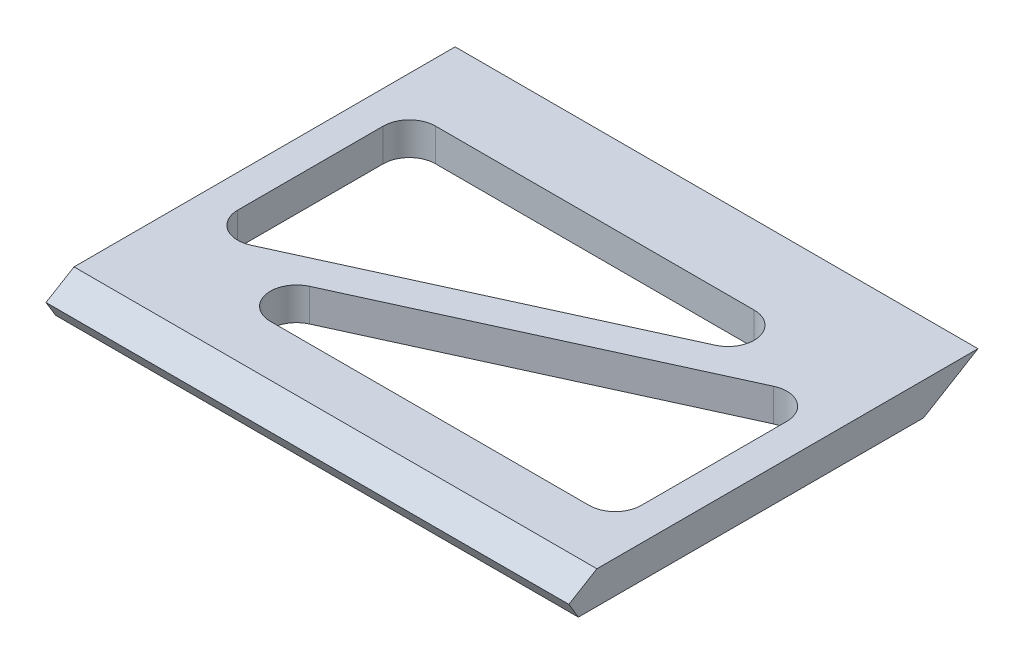
SolidWorks part; units mm, degrees
material "Balsa"
ref_plane "Front Plane" through (0, 0, 0) normal (0, 0, 1) x (1, 0, 0)
ref_plane "Top Plane" through (0, 0, 0) normal (0, 1, 0) x (1, 0, 0)
ref_plane "Right Plane" through (0, 0, 0) normal (1, 0, 0) x (0, 0, -1)
sketch "Sketch3" plane through (71.1933, 0, 0) normal (1, 0, 0) x (0, 0, -1)
  line L0 (56.968, 6.35) -> (46.3846, 0)
  line L1 (46.3846, 0) -> (-20.6804, 0)
  line L2 (-20.6804, 0) -> (-22.5302, 3.083)
  line L3 (-22.5302, 3.083) -> (-227.7008, 345.034) construction
  line L4 (56.968, 6.35) -> (63.7199, 10.4011) construction
  line L6 (-22.5302, 3.083) -> (-17.0851, 6.35)
  line L7 (-17.0851, 6.35) -> (56.968, 6.35)
extrude "Boss-Extrude2" add sketch "Sketch3" against normal up to surface (101.6 mm away)
sketch "Sketch4" plane through (0, 6.35, 0) normal (0, 1, 0) x (1, 0, 0)
  line L0 (-30.4067, -17.0851) -> (-30.4067, 56.968) construction
  line L1 (-18.9767, 41.728) -> (42.949, 41.728)
  line L2 (-24.0567, 36.648) -> (-24.0567, 8.3732)
  line L3 (-2.1624, -7.1791) -> (59.7633, -7.1791)
  line L4 (64.8433, 26.1757) -> (64.8433, -2.0991)
  line L5 (-30.4067, 56.968) -> (71.1933, 56.968) construction
  line L6 (71.1933, 56.968) -> (71.1933, -17.0851) construction
  line L7 (-30.4067, -17.0851) -> (71.1933, -17.0851) construction
  line L8 (-16.8668, 3.7521) -> (45.0589, 32.0269)
  line L9 (-4.2724, 2.522) -> (57.6533, 30.7968)
  line L10 (-29.6117, -5.5575) -> (68.6464, 39.3064)
  arc A0 (-4.2724, 2.522) -> (-2.1624, -7.1791) centre (-2.1624, -2.0991) ccw
  arc A1 (59.7633, -7.1791) -> (64.8433, -2.0991) centre (59.7633, -2.0991) ccw
  arc A2 (57.6533, 30.7968) -> (64.8433, 26.1757) centre (59.7633, 26.1757) cw
  arc A3 (45.0589, 32.0269) -> (42.949, 41.728) centre (42.949, 36.648) ccw
  arc A4 (-18.9767, 41.728) -> (-24.0567, 36.648) centre (-18.9767, 36.648) ccw
  arc A5 (-16.8668, 3.7521) -> (-24.0567, 8.3732) centre (-18.9767, 8.3732) cw
  dimension "D7" = 5.08
  dimension "D1" = 6.35
  dimension "D2" = 15.24
  dimension "D3" = 6.35
  dimension "D4" = 9.906
  dimension "D5" = 3.175
  dimension "D6" = 3.175
extrude "Cut-Extrude1" cut sketch "Sketch4" against normal up to surface (6.35 mm away) contours A5 L8 A3 L1 A4 L2 | A2 L9 A0 L3 A1 L4 region at (4.1335, 6.35, -27.6167) region at (36.6531, 6.35, -6.9321) up to face at (20.3933, 0, -12.8521)
